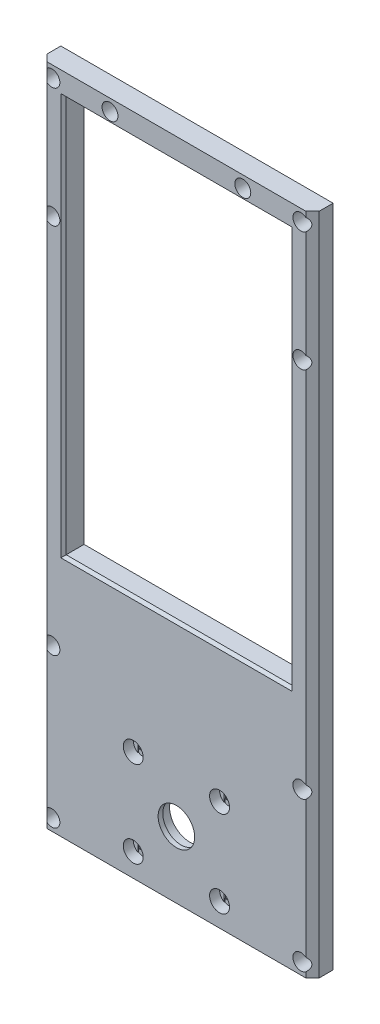
SolidWorks part; units mm, degrees
ref_plane "Front Plane" through (0, 0, 0) normal (0, 0, 1) x (1, 0, 0)
ref_plane "Top Plane" through (0, 0, 0) normal (0, 1, 0) x (1, 0, 0)
ref_plane "Right Plane" through (0, 0, 0) normal (1, 0, 0) x (0, 0, -1)
sketch "Sketch1" plane through (0, 0, 0) normal (0, 0, 1) x (1, 0, 0)
  line L1 (-41, -100) -> (41, -100)
  line L2 (-41, -100) -> (-41, 100)
  line L3 (-41, 100) -> (41, 100)
  line L4 (41, -100) -> (41, 100)
  line L5 (-41, -100) -> (41, 100) construction
  line L6 (-41, 100) -> (41, -100) construction
  line L7 (-34, -93) -> (34, -93)
  line L8 (-34, -93) -> (-34, 93)
  line L9 (-34, 93) -> (34, 93)
  line L10 (34, -93) -> (34, 93)
  line L11 (-34, -93) -> (34, 93) construction
  line L12 (-34, 93) -> (34, -93) construction
  point P0 (0, 0)
  point P6 (0, 0)
  dimension "D1" = 200
  dimension "D2" = 82
  dimension "D3" = 7
  dimension "D4" = 7
extrude "Boss-Extrude1" add sketch "Sketch1" along normal blind 7
sketch "Sketch2" plane through (0, 0, 7) normal (0, 0, 1) x (1, 0, 0)
  line L0 (34, -93) -> (34, 93) construction
  line L1 (-34, -93) -> (34, -93)
  line L2 (-34, -93) -> (-34, -57)
  line L3 (-34, -57) -> (34, -57)
  line L4 (34, -93) -> (34, -57)
  dimension "D1" = 36
extrude "Boss-Extrude2" add sketch "Sketch2" against normal up to surface (7 mm away) up to face at (0, 0, 0)
sketch "Sketch3" plane through (0, 0, 0) normal (0, 0, -1) x (-1, 0, 0)
  line L0 (0, -100) -> (0, -80) construction
  line L1 (41, -100) -> (-41, -100) construction
  circle A0 centre (0, -80) radius 5.5
  dimension "D1" = 11
  dimension "D2" = 20
extrude "Cut-Extrude1" cut sketch "Sketch3" against normal through all
sketch "Sketch4" plane through (0, 0, 0) normal (0, 0, -1) x (-1, 0, 0)
  circle A0 centre (0, -80) radius 6.05
  dimension "D1" = 12.1
extrude "Cut-Extrude2" cut sketch "Sketch4" against normal offset from surface (5.6 mm away) 1.4 up to face at (-5.5, -80, 7)
sketch "Sketch5" plane through (0, 0, 0) normal (0, 0, -1) x (-1, 0, 0)
  circle A0 centre (0, -80) radius 11
  dimension "D1" = 22
extrude "Cut-Extrude3" cut sketch "Sketch5" against normal offset from surface (3 mm away) 2.6 up to face at (-6.05, -80, 5.6)
sketch "Sketch6" plane through (0, 0, 0) normal (0, 0, -1) x (-1, 0, 0)
  line L1 (-13, -93) -> (13, -93) construction
  line L2 (-13, -93) -> (-13, -67) construction
  line L3 (-13, -67) -> (13, -67) construction
  line L4 (13, -93) -> (13, -67) construction
  line L5 (-13, -93) -> (13, -67) construction
  line L6 (-13, -67) -> (13, -93) construction
  circle A0 centre (-13, -67) radius 1.6
  circle A1 centre (13, -67) radius 1.6
  circle A2 centre (13, -93) radius 1.6
  circle A3 centre (-13, -93) radius 1.6
  point P0 (0, -80)
  dimension "D2" = 3.2
  dimension "D1" = 26
extrude "Cut-Extrude4" cut sketch "Sketch6" against normal through all
sketch "Sketch7" plane through (0, 0, 0) normal (0, 0, -1) x (-1, 0, 0)
  line L1 (-25, -99) -> (25, -99)
  line L2 (-25, -99) -> (-25, -61)
  line L3 (-25, -61) -> (25, -61)
  line L4 (25, -99) -> (25, -61)
  line L5 (-25, -99) -> (25, -61) construction
  line L6 (-25, -61) -> (25, -99) construction
  point P0 (0, -80)
  dimension "D1" = 50
  dimension "D2" = 38
extrude "Cut-Extrude5" cut sketch "Sketch7" against normal blind 1
sketch "Sketch8" plane through (0, 0, 7) normal (0, 0, 1) x (1, 0, 0)
  circle A0 centre (-13, -67) radius 3
  circle A1 centre (13, -67) radius 3
  circle A2 centre (13, -93) radius 3
  circle A3 centre (-13, -93) radius 3
  dimension "D1" = 6
extrude "Cut-Extrude6" cut sketch "Sketch8" against normal blind 3
sketch "Sketch9" plane through (0, 0, 7) normal (0, 0, 1) x (1, 0, 0)
  line L0 (-41, 100) -> (-41, -100) construction
  line L1 (-37.5, -96.5) -> (37.5, -96.5) construction
  line L2 (-37.5, -96.5) -> (-37.5, 96.5) construction
  line L3 (-37.5, 96.5) -> (37.5, 96.5) construction
  line L4 (37.5, -96.5) -> (37.5, 96.5) construction
  line L5 (-37.5, -96.5) -> (37.5, 96.5) construction
  line L6 (-37.5, 96.5) -> (37.5, -96.5) construction
  line L7 (41, 100) -> (-41, 100) construction
  circle A0 centre (-37.5, 96.5) radius 1.35
  circle A1 centre (37.5, 96.5) radius 1.35
  circle A4 centre (-37.5, -96.5) radius 1.35
  circle A5 centre (37.5, -96.5) radius 1.35
  circle A6 centre (-37.5, 60.5) radius 1.35
  circle A7 centre (37.5, 60.5) radius 1.35
  circle A8 centre (37.5, -51.5) radius 1.35
  circle A9 centre (-37.5, -51.5) radius 1.35
  point P0 (0, 0)
  dimension "D3" = 2.7
  dimension "D1" = 3.5
  dimension "D2" = 3.5
  dimension "D4" = 45
  dimension "D5" = 36
extrude "Cut-Extrude7" cut sketch "Sketch9" against normal through all
sketch "Sketch10" plane through (0, 0, 7) normal (0, 0, 1) x (1, 0, 0)
  circle A0 centre (-37.5, 96.5) radius 2.4
  circle A1 centre (37.5, 60.5) radius 2.4
  circle A2 centre (-37.5, 60.5) radius 2.4
  circle A3 centre (37.5, 96.5) radius 2.4
  circle A4 centre (-37.5, -96.5) radius 2.4
  circle A5 centre (37.5, -96.5) radius 2.4
  circle A6 centre (-37.5, -51.5) radius 2.4
  circle A7 centre (37.5, -51.5) radius 2.4
  dimension "D1" = 4.8
extrude "Cut-Extrude8" cut sketch "Sketch10" against normal blind 5
chamfer "Chamfer1" distance 2 angle 45 2 edges at (-41, 0, 7) (41, 0, 7)
sketch "Sketch11" plane through (0, 0, 7) normal (0, 0, 1) x (1, 0, 0)
  line L0 (34, -57) -> (34, 93) construction
  line L1 (-34, -57) -> (34, -57)
  line L2 (-34, -57) -> (-34, -26.5)
  line L3 (-34, -26.5) -> (34, -26.5)
  line L4 (34, -57) -> (34, -26.5)
  line L5 (-39, -100) -> (39, -100) construction
  dimension "D1" = 73.5
extrude "Boss-Extrude3" add sketch "Sketch11" against normal up to surface (7 mm away) up to face at (-36.15, -96.5, 0)
sketch "Sketch12" plane through (0, 0, 7) normal (0, 0, 1) x (1, 0, 0)
  line L0 (-37.5, 96.5) -> (37.5, 96.5) construction
  line L1 (-20, 96.5) -> (20, 96.5) construction
  circle A0 centre (-20, 96.5) radius 1.35
  circle A1 centre (20, 96.5) radius 1.35
  circle A2 centre (-37.5, 96.5) radius 1.35 construction
  point P7 (0, 96.5)
  dimension "D1" = 40
extrude "Cut-Extrude9" cut sketch "Sketch12" against normal through all
sketch "Sketch13" plane through (0, 0, 7) normal (0, 0, 1) x (1, 0, 0)
  circle A0 centre (-20, 96.5) radius 2.4
  circle A1 centre (20, 96.5) radius 2.4
  circle A2 centre (-37.5, 96.5) radius 2.4 construction
extrude "Cut-Extrude10" cut sketch "Sketch13" against normal up to surface (5 mm away) up to face at (-35.1, 96.5, 2)
chamfer "Chamfer2" distance 0.8 angle 45 12 edges at (0, -100, 0) (-41, 0, 0) (0, 100, 0) (41, 0, 0) (34, 33.25, 7) (0, 93, 7) (-34, 33.25, 7) (0, -26.5, 7) (-34, 33.25, 0) (0, 93, 0) (34, 33.25, 0) (0, -26.5, 0)
sketch "Sketch14" plane through (0, 0, 2) normal (0, 0, 1) x (1, 0, 0)
  line L2 (-38.85, -53.4843) -> (-38.85, -49.5157)
  line L4 (-36.15, -53.4843) -> (-36.15, -49.5157)
  line L5 (-38.85, -53.4843) -> (-36.15, -49.5157) construction
  line L6 (-38.85, -49.5157) -> (-36.15, -53.4843) construction
  line L14 (-38.85, -98.4843) -> (-38.85, -94.5157)
  line L16 (-36.15, -98.4843) -> (-36.15, -94.5157)
  line L17 (-38.85, -98.4843) -> (-36.15, -94.5157) construction
  line L18 (-38.85, -94.5157) -> (-36.15, -98.4843) construction
  line L26 (-38.85, 58.5157) -> (-38.85, 62.4843)
  line L28 (-36.15, 58.5157) -> (-36.15, 62.4843)
  line L29 (-38.85, 58.5157) -> (-36.15, 62.4843) construction
  line L30 (-38.85, 62.4843) -> (-36.15, 58.5157) construction
  line L32 (-21.35, 94.5157) -> (-21.35, 98.4843)
  line L34 (-18.65, 94.5157) -> (-18.65, 98.4843)
  line L35 (-21.35, 94.5157) -> (-18.65, 98.4843) construction
  line L36 (-21.35, 98.4843) -> (-18.65, 94.5157) construction
  line L38 (-38.85, 94.5157) -> (-38.85, 98.4843)
  line L40 (-36.15, 94.5157) -> (-36.15, 98.4843)
  line L41 (-38.85, 94.5157) -> (-36.15, 98.4843) construction
  line L42 (-38.85, 98.4843) -> (-36.15, 94.5157) construction
  arc A0 (-39, -53.3735) -> (-39, -49.6265) centre (-37.5, -51.5) ccw construction
  circle A2 centre (-37.5, -96.5) radius 2.4 construction
  circle A4 centre (-37.5, 60.5) radius 2.4 construction
  circle A5 centre (-20, 96.5) radius 2.4 construction
  circle A6 centre (-37.5, 96.5) radius 2.4 construction
  circle A7 centre (-37.5, 96.5) radius 1.35 construction
  circle A8 centre (-20, 96.5) radius 1.35 construction
  circle A9 centre (-37.5, 60.5) radius 1.35 construction
  circle A10 centre (-37.5, -51.5) radius 1.35 construction
  circle A12 centre (-37.5, -96.5) radius 1.35 construction
  arc A16 (-21.35, 94.5157) -> (-18.65, 94.5157) centre (-20, 96.5) ccw
  arc A17 (-36.15, 98.4843) -> (-38.85, 98.4843) centre (-37.5, 96.5) ccw
  arc A18 (-36.15, 62.4843) -> (-38.85, 62.4843) centre (-37.5, 60.5) ccw
  arc A20 (-38.85, -53.4843) -> (-36.15, -53.4843) centre (-37.5, -51.5) ccw
  arc A22 (-36.15, -94.5157) -> (-38.85, -94.5157) centre (-37.5, -96.5) ccw
  arc A23 (-38.85, 94.5157) -> (-36.15, 94.5157) centre (-37.5, 96.5) ccw
  arc A24 (-18.65, 98.4843) -> (-21.35, 98.4843) centre (-20, 96.5) ccw
  arc A25 (-38.85, 58.5157) -> (-36.15, 58.5157) centre (-37.5, 60.5) ccw
  arc A26 (-36.15, -49.5157) -> (-38.85, -49.5157) centre (-37.5, -51.5) ccw
  arc A29 (-38.85, -98.4843) -> (-36.15, -98.4843) centre (-37.5, -96.5) ccw
  point P0 (-37.5, -51.5)
  point P17 (-37.5, -96.5)
  point P33 (-37.5, 60.5)
  point P41 (-20, 96.5)
  point P49 (-37.5, 96.5)
extrude "Cut-Extrude11" cut sketch "Sketch14" against normal blind 0.2
sketch "Sketch15" plane through (0, 0, 1.8) normal (0, 0, 1) x (1, 0, 0)
  line L0 (-36.15, -96.5) -> (-36.15, -94.5157) construction
  line L1 (-38.85, -97.85) -> (-36.15, -97.85)
  line L2 (-38.85, -97.85) -> (-38.85, -95.15)
  line L3 (-38.85, -95.15) -> (-36.15, -95.15)
  line L4 (-36.15, -97.85) -> (-36.15, -95.15)
  line L5 (-38.85, -97.85) -> (-36.15, -95.15) construction
  line L6 (-38.85, -95.15) -> (-36.15, -97.85) construction
  line L7 (-36.15, 60.5) -> (-36.15, 62.4843) construction
  line L8 (-38.85, -52.85) -> (-36.15, -52.85)
  line L9 (-38.85, -52.85) -> (-38.85, -50.15)
  line L10 (-38.85, -50.15) -> (-36.15, -50.15)
  line L11 (-36.15, -52.85) -> (-36.15, -50.15)
  line L12 (-38.85, -52.85) -> (-36.15, -50.15) construction
  line L13 (-38.85, -50.15) -> (-36.15, -52.85) construction
  line L14 (-38.85, 59.15) -> (-36.15, 59.15)
  line L15 (-38.85, 59.15) -> (-38.85, 61.85)
  line L16 (-38.85, 61.85) -> (-36.15, 61.85)
  line L17 (-36.15, 59.15) -> (-36.15, 61.85)
  line L18 (-38.85, 59.15) -> (-36.15, 61.85) construction
  line L19 (-38.85, 61.85) -> (-36.15, 59.15) construction
  line L20 (-36.15, 94.5157) -> (-36.15, 98.4843) construction
  line L21 (-38.85, 95.15) -> (-36.15, 95.15)
  line L22 (-38.85, 95.15) -> (-38.85, 97.85)
  line L23 (-38.85, 97.85) -> (-36.15, 97.85)
  line L24 (-36.15, 95.15) -> (-36.15, 97.85)
  line L25 (-38.85, 95.15) -> (-36.15, 97.85) construction
  line L26 (-38.85, 97.85) -> (-36.15, 95.15) construction
  line L27 (-18.65, 94.5157) -> (-18.65, 98.4843) construction
  line L28 (-21.35, 95.15) -> (-18.65, 95.15)
  line L29 (-21.35, 95.15) -> (-21.35, 97.85)
  line L30 (-21.35, 97.85) -> (-18.65, 97.85)
  line L31 (-18.65, 95.15) -> (-18.65, 97.85)
  line L32 (-21.35, 95.15) -> (-18.65, 97.85) construction
  line L33 (-21.35, 97.85) -> (-18.65, 95.15) construction
  arc A0 (-36.15, -51.5) -> (-38.85, -51.5) centre (-37.5, -51.5) ccw construction
  arc A1 (-36.15, 60.5) -> (-38.85, 60.5) centre (-37.5, 60.5) ccw construction
  arc A2 (-18.65, 96.5) -> (-21.35, 96.5) centre (-20, 96.5) ccw construction
  arc A3 (-36.15, 96.5) -> (-38.85, 96.5) centre (-37.5, 96.5) ccw construction
  point P0 (-37.5, -96.5)
  point P8 (-37.5, -51.5)
  point P17 (-37.5, 60.5)
  point P28 (-37.5, 96.5)
  point P36 (-20, 96.5)
extrude "Cut-Extrude12" cut sketch "Sketch15" against normal blind 0.2
sketch "Sketch16" plane through (0, 0, 4) normal (0, 0, 1) x (1, 0, 0)
  line L2 (-14.6, -69.5377) -> (-14.6, -64.4623)
  line L4 (-11.4, -69.5377) -> (-11.4, -64.4623)
  line L5 (-14.6, -69.5377) -> (-11.4, -64.4623) construction
  line L6 (-14.6, -64.4623) -> (-11.4, -69.5377) construction
  line L8 (-14.6, -95.5377) -> (-14.6, -90.4623)
  line L10 (-11.4, -95.5377) -> (-11.4, -90.4623)
  line L11 (-14.6, -95.5377) -> (-11.4, -90.4623) construction
  line L12 (-14.6, -90.4623) -> (-11.4, -95.5377) construction
  circle A0 centre (-13, -67) radius 3 construction
  circle A1 centre (-13, -93) radius 3 construction
  circle A2 centre (-13, -93) radius 1.6 construction
  circle A3 centre (-13, -67) radius 1.6 construction
  circle A4 centre (-13, -93) radius 3 construction
  circle A5 centre (-13, -67) radius 3 construction
  arc A6 (-11.4, -90.4623) -> (-14.6, -90.4623) centre (-13, -93) ccw
  arc A7 (-14.6, -69.5377) -> (-11.4, -69.5377) centre (-13, -67) ccw
  arc A8 (-11.4, -64.4623) -> (-14.6, -64.4623) centre (-13, -67) ccw
  arc A9 (-14.6, -95.5377) -> (-11.4, -95.5377) centre (-13, -93) ccw
  point P0 (-13, -67)
  point P8 (-13, -93)
extrude "Cut-Extrude13" cut sketch "Sketch16" against normal blind 0.2
sketch "Sketch17" plane through (0, 0, 3.8) normal (0, 0, 1) x (1, 0, 0)
  line L0 (-11.4, -69.5377) -> (-11.4, -64.4623) construction
  line L1 (-14.6, -68.6) -> (-11.4, -68.6)
  line L2 (-14.6, -68.6) -> (-14.6, -65.4)
  line L3 (-14.6, -65.4) -> (-11.4, -65.4)
  line L4 (-11.4, -68.6) -> (-11.4, -65.4)
  line L5 (-14.6, -68.6) -> (-11.4, -65.4) construction
  line L6 (-14.6, -65.4) -> (-11.4, -68.6) construction
  line L7 (-11.4, -95.5377) -> (-11.4, -90.4623) construction
  line L8 (-14.6, -94.6) -> (-11.4, -94.6)
  line L9 (-14.6, -94.6) -> (-14.6, -91.4)
  line L10 (-14.6, -91.4) -> (-11.4, -91.4)
  line L11 (-11.4, -94.6) -> (-11.4, -91.4)
  line L12 (-14.6, -94.6) -> (-11.4, -91.4) construction
  line L13 (-14.6, -91.4) -> (-11.4, -94.6) construction
  arc A0 (-11.4, -93) -> (-14.6, -93) centre (-13, -93) ccw construction
  arc A1 (-11.4, -67) -> (-14.6, -67) centre (-13, -67) ccw construction
  point P0 (-13, -67)
  point P8 (-13, -93)
extrude "Cut-Extrude14" cut sketch "Sketch17" against normal blind 0.2
mirror "Mirror1" about plane through (0, 0, 0) normal (1, 0, 0) of "Cut-Extrude12", "Cut-Extrude13", "Cut-Extrude14", "Cut-Extrude11"
